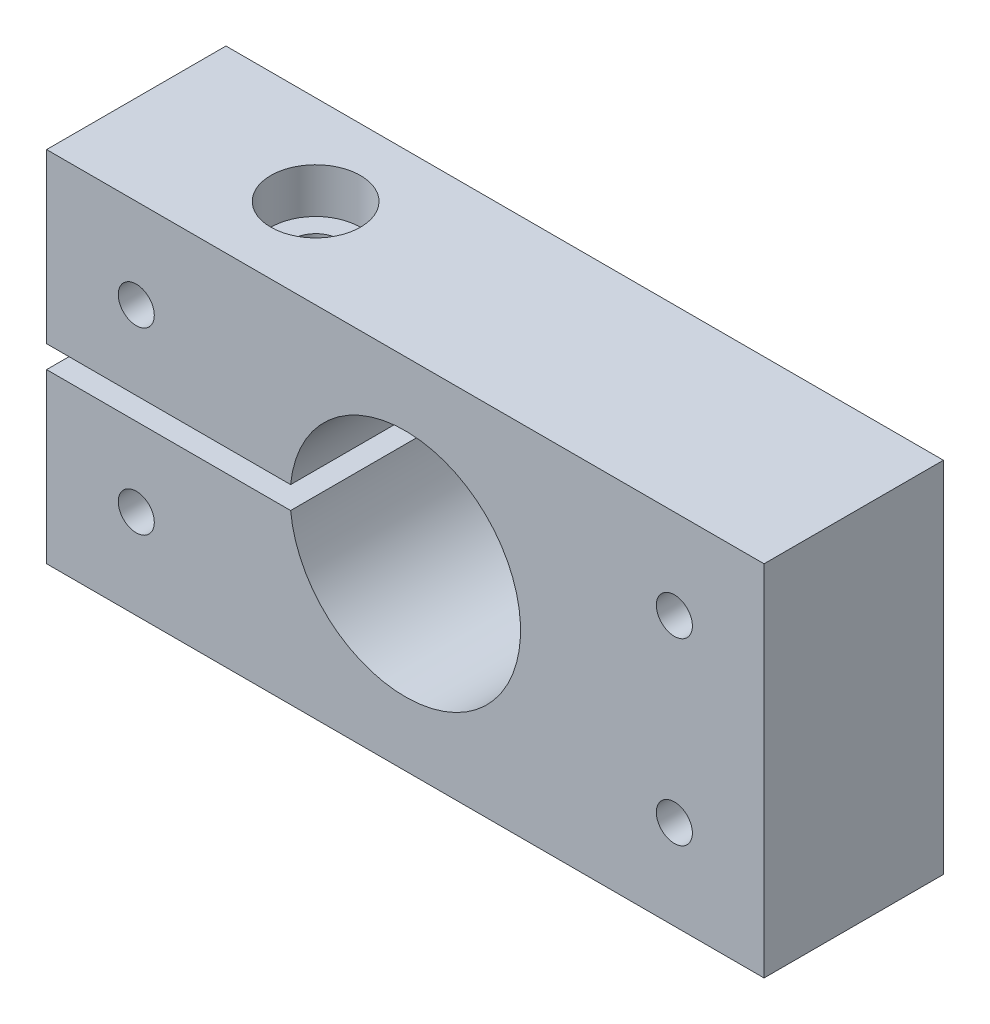
SolidWorks part; units mm, degrees
ref_plane "Front" through (0, 0, 0) normal (0, 0, 1) x (1, 0, 0)
ref_plane "Top" through (0, 0, 0) normal (0, 1, 0) x (1, 0, 0)
ref_plane "Right" through (0, 0, 0) normal (1, 0, 0) x (0, 0, -1)
sketch "Sketch1" plane through (0, 0, 0) normal (0, 1, 0) x (1, 0, 0)
  line L1 (-50.8, -12.7) -> (50.8, -12.7)
  line L2 (-50.8, -12.7) -> (-50.8, 12.7)
  line L3 (-50.8, 12.7) -> (50.8, 12.7)
  line L4 (50.8, -12.7) -> (50.8, 12.7)
  line L5 (-50.8, -12.7) -> (50.8, 12.7) construction
  line L6 (-50.8, 12.7) -> (50.8, -12.7) construction
  point P0 (0, 0)
  dimension "D1" = 101.6
  dimension "D2" = 25.4
extrude "Boss-Extrude1" add sketch "Sketch1" along normal mid plane 50.8 contours L3 L4 L1 L2
sketch "Sketch2" plane through (0, 0, 12.7) normal (0, 0, 1) x (1, 0, 0)
  circle A0 centre (0, 0) radius 16.3195
  dimension "D1" = 32.639
extrude "Cut-Extrude1" cut sketch "Sketch2" against normal up to next contours A0
sketch "Sketch3" plane through (0, 0, 12.7) normal (0, 0, 1) x (1, 0, 0)
  line L0 (50.8, 25.4) -> (50.8, -25.4) construction
  line L1 (-38.1, -12.7) -> (-38.1, 12.7) construction
  line L2 (-38.1, 12.7) -> (38.1, 12.7) construction
  line L3 (50, 0) -> (-50, 0) construction
  line L4 (0, -50) -> (0, 50) construction
  point P0 (-38.1, 12.7)
  point P1 (-38.1, -12.7)
  point P2 (38.1, 12.7)
  point P3 (38.1, -12.7)
  point P5 (-38.1, 0)
  point P12 (0, 12.7)
  dimension "D1" = 12.7
  dimension "D2" = 25.4
hole_wizard "1/4-20 Tapped Hole1" positions "Sketch4" profile "Sketch5" tap size "1/4-20" standard "ANSI Inch" end condition through all
sketch "Sketch4" plane through (0, 0, 12.7) normal (0, 0, 1) x (1, 0, 0)
  point P0 (-38.1, 12.7)
  point P3 (-38.1, -12.7)
  point P6 (38.1, 12.7)
  point P9 (38.1, -12.7)
sketch "Sketch5" plane through (-38.1, 12.7, 12.7) normal (1, 0, 0) x (0, -1, 0)
  line L0 (0, 0) -> (0, 25.4)
  line L1 (0, 25.4) -> (2.5527, 25.4)
  line L2 (2.5527, 25.4) -> (2.5527, 0)
  line L5 (2.5527, 0) -> (0, 0)
  line L11 (0, -6.35) -> (0, 107.95) construction
  dimension "Thru Tap Drill Dia." = 5.1054
  dimension "Thru Tap Drill Depth" = 25.4
sketch "Sketch6" plane through (0, 0, 12.7) normal (0, 0, 1) x (1, 0, 0)
  line L0 (-50.8, 25.4) -> (-50.8, -25.4) construction
  line L1 (-50.8, 1.5875) -> (0, 1.5875)
  line L2 (-50.8, 1.5875) -> (-50.8, -1.5875)
  line L3 (-50.8, -1.5875) -> (0, -1.5875)
  line L4 (0, 1.5875) -> (0, -1.5875)
  line L5 (0, -50) -> (0, 50) construction
  line L6 (50, 0) -> (-50, 0) construction
  point P8 (0, 0)
  dimension "D1" = 3.175
extrude "Cut-Extrude2" cut sketch "Sketch6" against normal up to next
sketch "Sketch7" plane through (0, 25.4, 0) normal (0, 1, 0) x (1, 0, 0)
  line L0 (-50, 0) -> (50, 0) construction
  line L1 (-50.8, -12.7) -> (-50.8, 12.7) construction
  point P0 (-25.4, 0)
  dimension "D1" = 25.4
hole_wizard "CBORE for 1/4 Socket Head Cap Screw1" positions "Sketch8" profile "Sketch10" counterbore size "1/4" standard "ANSI Inch" end condition up to next
sketch "Sketch8" plane through (0, 25.4, 0) normal (0, 1, 0) x (1, 0, 0)
  point P0 (-25.4, 0)
sketch "Sketch10" plane through (-25.4, 25.4, 0) normal (1, 0, 0) x (0, 0, 1)
  line L0 (0, 0) -> (0, 23.8125)
  line L1 (0, 23.8125) -> (3.3782, 23.8125)
  line L3 (3.3782, 23.8125) -> (3.3782, 6.35)
  line L4 (3.3782, 6.35) -> (6.35, 6.35)
  line L5 (6.35, 6.35) -> (6.35, 0)
  line L7 (6.35, 0) -> (0, 0)
  line L11 (0, -6.35) -> (0, 107.95) construction
  dimension "Thru Hole Dia." = 6.7564
  dimension "Thru Hole Depth" = 23.8125
  dimension "C'Bore Dia." = 12.7
  dimension "C'Bore Depth" = 6.35
hole_wizard "1/4-20 Tapped Hole2" positions "Sketch11" profile "Sketch13" tap size "1/4-20" standard "ANSI Inch" end condition through all
sketch "Sketch11" plane through (0, -1.5875, 0) normal (0, 1, 0) x (1, 0, 0)
  point P0 (-25.4, 0)
sketch "Sketch13" plane through (-25.4, -1.5875, 0) normal (1, 0, 0) x (0, 0, 1)
  line L0 (0, 0) -> (0, 23.8125)
  line L1 (0, 23.8125) -> (2.5527, 23.8125)
  line L2 (2.5527, 23.8125) -> (2.5527, 0)
  line L5 (2.5527, 0) -> (0, 0)
  line L11 (0, -6.35) -> (0, 107.95) construction
  dimension "Thru Tap Drill Dia." = 5.1054
  dimension "Thru Tap Drill Depth" = 23.8125
cosmetic thread "Hole Thread1" parameters "D2"=6.35
